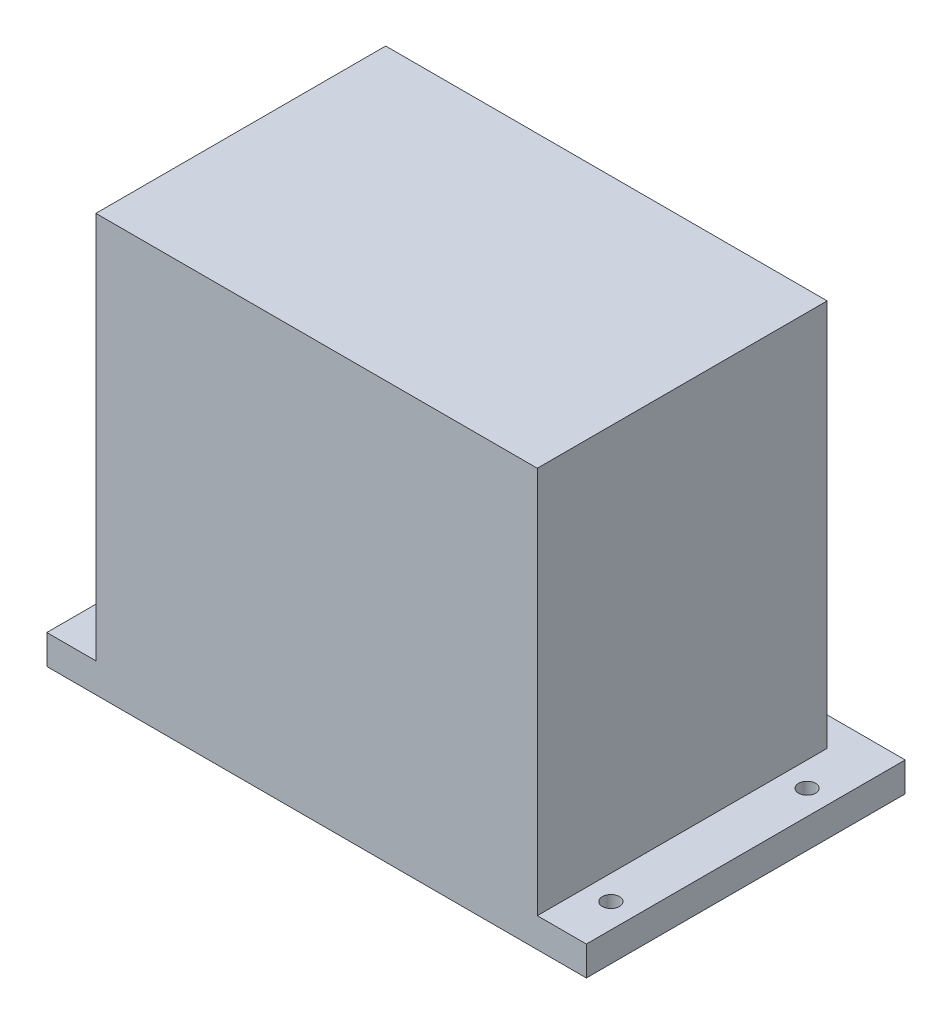
SolidWorks part; units mm, degrees
ref_plane "Front Plane" through (0, 0, 0) normal (0, 0, 1) x (1, 0, 0)
ref_plane "Top Plane" through (0, 0, 0) normal (0, 1, 0) x (1, 0, 0)
ref_plane "Right Plane" through (0, 0, 0) normal (1, 0, 0) x (0, 0, -1)
sketch "Sketch1" plane through (0, 0, 0) normal (0, 1, 0) x (1, 0, 0)
  line L0 (-35, 32.5) -> (-35, 27.5)
  line L1 (-55, -32.5) -> (55, -32.5)
  line L2 (-55, -32.5) -> (-55, 32.5)
  line L3 (-55, 32.5) -> (-35, 32.5)
  line L4 (55, -32.5) -> (55, 32.5)
  line L5 (-55, -32.5) -> (55, 32.5) construction
  line L6 (-55, 32.5) -> (55, -32.5) construction
  line L7 (-35, 27.5) -> (-15, 27.5)
  line L8 (-15, 27.5) -> (-15, 32.5)
  line L9 (0, -55) -> (0, 55) construction
  line L10 (15, 27.5) -> (15, 32.5)
  line L11 (35, 32.5) -> (35, 27.5)
  line L12 (35, 27.5) -> (15, 27.5)
  line L13 (-15, 32.5) -> (15, 32.5)
  line L14 (35, 32.5) -> (55, 32.5)
  line L15 (-45, -32.5) -> (-45, 26.5909)
  line L16 (-45, 26.5909) -> (45, 26.5909)
  line L17 (45, 26.5909) -> (45, -32.5)
  circle A0 centre (50, 17.5) radius 1.75
  circle A1 centre (50, -22.5) radius 1.75
  circle A2 centre (-50, -22.5) radius 1.75
  circle A3 centre (-50, 17.5) radius 1.75
  point P0 (0, 0)
  dimension "D3" = 3.5
  dimension "D1" = 110
  dimension "D2" = 65
  dimension "D4" = 40
  dimension "D5" = 5
  dimension "D6" = 5
  dimension "D7" = 10
  dimension "D8" = 20
  dimension "D9" = 5
  dimension "D10" = 20
  dimension "D11" = 90
extrude "Boss-Extrude1" add sketch "Sketch1" along normal blind 6 contours L16 L17 L1 L4 L14 L11 L12 L10 L13 L8 L7 L0 L3 L2 L15 A3 A2 A1 A0 region at (-36.2777, 0, -30)
extrude "Boss-Extrude2" add sketch "Sketch1<3>" along normal blind 85 contours L17 L16 L15 L1 region at (0, 0, 2.9545)
sketch "Sketch1<3>" plane through (0, 0, 0) normal (0, 1, 0) x (1, 0, 0) same geometry as "Sketch1"
